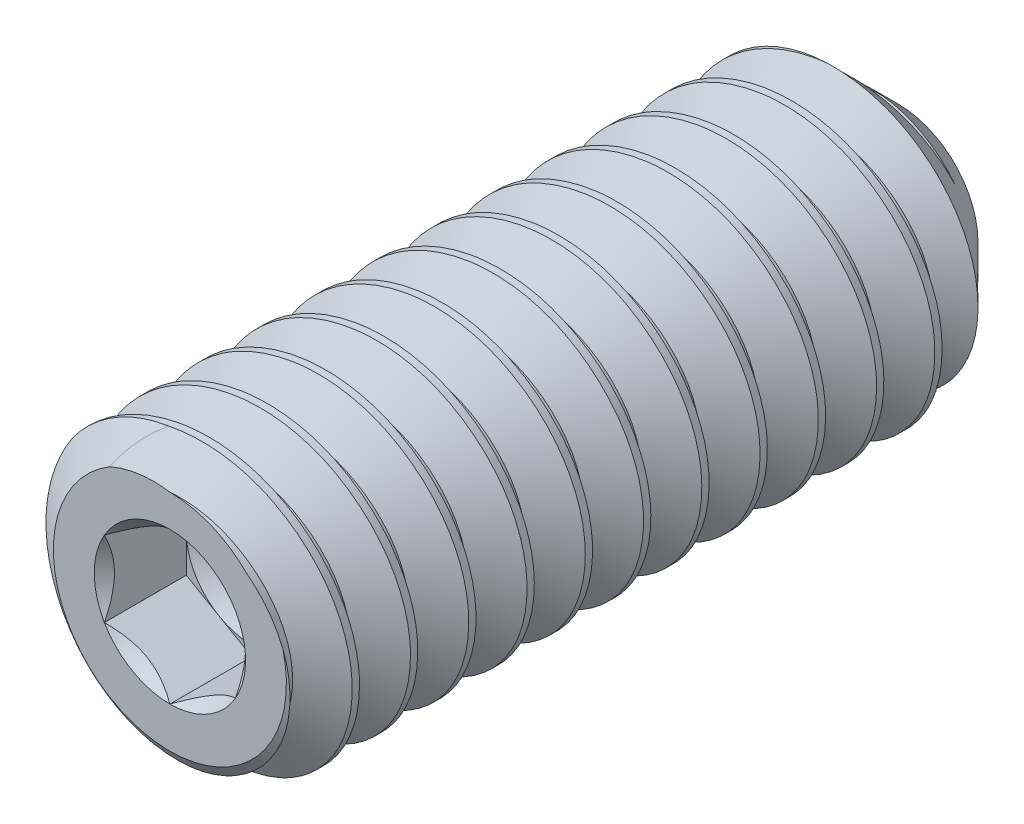
SolidWorks part; units mm, degrees
ref_plane "Front" through (0, 0, 0) normal (0, 0, 1) x (1, 0, 0)
ref_plane "Top" through (0, 0, 0) normal (0, 1, 0) x (1, 0, 0)
ref_plane "Right" through (0, 0, 0) normal (1, 0, 0) x (0, 0, -1)
sketch "Sketch22" plane through (0, 0, 0) normal (1, 0, 0) x (0, 0, -1)
  line L0 (-2.3354, 0) -> (-2.3354, 0.8)
  line L1 (-2.3354, 0.8) -> (-2.1953, 1)
  line L2 (-2.1953, 1) -> (2.2126, 1)
  line L3 (2.2126, 1) -> (2.6646, 0.548)
  line L4 (2.6646, 0.548) -> (2.3354, 0)
  line L5 (2.3354, 0) -> (-2.3354, 0)
  line L6 (2.3354, 0) -> (2.6646, 0) construction
  line L7 (2.6646, 0) -> (2.6646, 0.548) construction
  line L8 (2.6646, -0.548) -> (2.3354, 0) construction
  line L9 (-2.1953, -1) -> (2.2126, -1) construction
  dimension "Dia" = 2
  dimension "Length" = 5
  dimension "D3" = 35
  dimension "D5" = 118
  dimension "D6" = 45
  dimension "D7" = 1.6
revolve "Revolve1" add sketch "Sketch22" angle 360 about L6
ref_plane "Plane1" through (0, 0, -2.6646) normal (0, 0, 1) x (1, 0, 0)
sketch "Sketch27" plane through (0, 0, -2.6646) normal (0, 0, 1) x (1, 0, 0)
  circle A0 centre (0, 0) radius 1 construction
  circle A1 centre (0, 0) radius 1
curve "Helix/Spiral1" pitch 0.4 height 5.4 turns 13.5
sketch "Sketch28" plane through (0, 0, 0) normal (1, 0, 0) x (0, 0, -1)
  line L0 (2.6646, 1) -> (3.0146, 1)
  line L1 (3.0146, 1) -> (2.8646, 0.7402)
  line L2 (2.8646, 0.7402) -> (2.8146, 0.7402)
  line L3 (2.8146, 0.7402) -> (2.6646, 1)
  line L4 (2.7396, 0.8701) -> (2.9396, 0.8701) construction
  line L6 (-2.1953, 1) -> (2.2126, 1) construction
  dimension "D1" = 0.05
  dimension "D2" = 0.2
  dimension "D3" = 60
sweep "Cut-Sweep2" cut profiles "Sketch28" path "Helix/Spiral1"
sketch "Sketch23" plane through (0, 0, 2.3354) normal (0, 0, 1) x (1, 0, 0)
  line L1 (0, 0.5196) -> (-0.45, 0.2598)
  line L2 (-0.45, 0.2598) -> (-0.45, -0.2598)
  line L3 (-0.45, -0.2598) -> (0, -0.5196)
  line L4 (0, -0.5196) -> (0.45, -0.2598)
  line L5 (0.45, -0.2598) -> (0.45, 0.2598)
  line L6 (0.45, 0.2598) -> (0, 0.5196)
  circle A0 centre (0, 0) radius 0.45 construction
  dimension "Hex" = 0.9
extrude "Cut-Extrude10" cut sketch "Sketch23" against normal blind 0.5625
sketch "Sketch24" plane through (0, 0, 2.3354) normal (0, 0, 1) x (1, 0, 0)
  circle A0 centre (0, 0) radius 0.5196
extrude "Cut-Extrude11" cut sketch "Sketch24" against normal through all draft 45
sketch "Sketch26" plane through (0, 0, 1.7729) normal (0, 0, 1) x (1, 0, 0)
  circle A0 centre (0, 0) radius 0.45 construction
  circle A1 centre (0, 0) radius 0.45
extrude "Cut-Extrude12" cut sketch "Sketch26" against normal through all draft 60
sketch "Sketch30" plane through (0, 0, 0) normal (1, 0, 0) x (0, 0, -1)
  line L0 (-2.1953, 1) -> (2.2126, 1) construction
  line L1 (-2.3354, 0) -> (-2.3354, 0.8) construction
  line L2 (2.6646, 0) -> (2.6646, 0.548) construction
  line L3 (-2.1953, -1) -> (2.2126, -1) construction
  point P0 (-2.3354, 1)
  point P1 (2.6646, 1)
  point P2 (2.6646, -1)
  point P11 (2.0646, -1)
  dimension "D1" = 0.6
sketch "Sketch31" plane through (0, 0, 0) normal (1, 0, 0) x (0, 0, -1)
  line L2 (2.3354, 0) -> (2.6646, -0.548)
  line L3 (2.6646, 0.548) -> (2.3354, 0)
equation "\"D7@Sketch22\"=\"Dia@Sketch22\"*.8"
equation "\"D1@Sketch28\" = \"D4@Helix/Spiral1\" * .125"
equation "\"D2@Sketch28\" = \"D4@Helix/Spiral1\" * .5"
equation "\"D3@Helix/Spiral1\" = \"Length@Sketch22\" + \"D4@Helix/Spiral1\""
equation "\"D1@Sketch30\" = \"D4@Helix/Spiral1\" * 1.5"
equation "\"hex Depth@Cut-Extrude10\" = \"Hex@Sketch23\" * .625"
